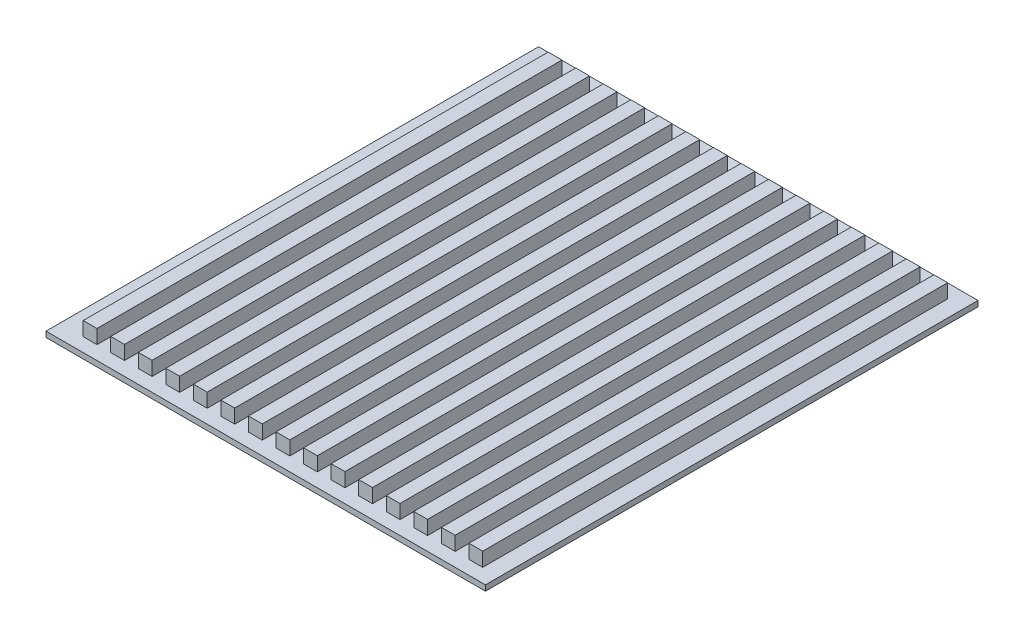
SolidWorks part; units mm, degrees
ref_plane "Front Plane" through (0, 0, 0) normal (0, 0, 1) x (1, 0, 0)
ref_plane "Top Plane" through (0, 0, 0) normal (0, 1, 0) x (1, 0, 0)
ref_plane "Right Plane" through (0, 0, 0) normal (1, 0, 0) x (0, 0, -1)
sketch "Sketch1" plane through (0, 0, 0) normal (0, 0, 1) x (1, 0, 0)
  line L0 (-297.4715, 336.2025) -> (7.3285, 336.2025) construction
  line L1 (-0.6715, 336.2025) -> (-10.6715, 336.2025)
  line L2 (-0.6715, 336.2025) -> (-0.6715, 322.0044)
  line L3 (-0.6715, 322.0044) -> (-10.6715, 322.0044)
  line L4 (-10.6715, 336.2025) -> (-10.6715, 322.0044)
  line L5 (7.3285, 326.0425) -> (7.3285, 336.2025) construction
  line L6 (-30.6715, 336.2025) -> (-30.6715, 322.0044)
  line L7 (-20.6715, 322.0044) -> (-30.6715, 322.0044)
  line L8 (-20.6715, 336.2025) -> (-20.6715, 322.0044)
  line L9 (-20.6715, 336.2025) -> (-30.6715, 336.2025)
  line L10 (-50.6715, 336.2025) -> (-50.6715, 322.0044)
  line L11 (-40.6715, 322.0044) -> (-50.6715, 322.0044)
  line L12 (-40.6715, 336.2025) -> (-40.6715, 322.0044)
  line L13 (-40.6715, 336.2025) -> (-50.6715, 336.2025)
  line L14 (-70.6715, 336.2025) -> (-70.6715, 322.0044)
  line L15 (-60.6715, 322.0044) -> (-70.6715, 322.0044)
  line L16 (-60.6715, 336.2025) -> (-60.6715, 322.0044)
  line L17 (-60.6715, 336.2025) -> (-70.6715, 336.2025)
  line L18 (-90.6715, 336.2025) -> (-90.6715, 322.0044)
  line L19 (-80.6715, 322.0044) -> (-90.6715, 322.0044)
  line L20 (-80.6715, 336.2025) -> (-80.6715, 322.0044)
  line L21 (-80.6715, 336.2025) -> (-90.6715, 336.2025)
  line L22 (-110.6715, 336.2025) -> (-110.6715, 322.0044)
  line L23 (-100.6715, 322.0044) -> (-110.6715, 322.0044)
  line L24 (-100.6715, 336.2025) -> (-100.6715, 322.0044)
  line L25 (-100.6715, 336.2025) -> (-110.6715, 336.2025)
  line L26 (-130.6715, 336.2025) -> (-130.6715, 322.0044)
  line L27 (-120.6715, 322.0044) -> (-130.6715, 322.0044)
  line L28 (-120.6715, 336.2025) -> (-120.6715, 322.0044)
  line L29 (-120.6715, 336.2025) -> (-130.6715, 336.2025)
  line L30 (-150.6715, 336.2025) -> (-150.6715, 322.0044)
  line L31 (-140.6715, 322.0044) -> (-150.6715, 322.0044)
  line L32 (-140.6715, 336.2025) -> (-140.6715, 322.0044)
  line L33 (-140.6715, 336.2025) -> (-150.6715, 336.2025)
  line L34 (-170.6715, 336.2025) -> (-170.6715, 322.0044)
  line L35 (-160.6715, 322.0044) -> (-170.6715, 322.0044)
  line L36 (-160.6715, 336.2025) -> (-160.6715, 322.0044)
  line L37 (-160.6715, 336.2025) -> (-170.6715, 336.2025)
  line L38 (-190.6715, 336.2025) -> (-190.6715, 322.0044)
  line L39 (-180.6715, 322.0044) -> (-190.6715, 322.0044)
  line L40 (-180.6715, 336.2025) -> (-180.6715, 322.0044)
  line L41 (-180.6715, 336.2025) -> (-190.6715, 336.2025)
  line L42 (-210.6715, 336.2025) -> (-210.6715, 322.0044)
  line L43 (-200.6715, 322.0044) -> (-210.6715, 322.0044)
  line L44 (-200.6715, 336.2025) -> (-200.6715, 322.0044)
  line L45 (-200.6715, 336.2025) -> (-210.6715, 336.2025)
  line L46 (-230.6715, 336.2025) -> (-230.6715, 322.0044)
  line L47 (-220.6715, 322.0044) -> (-230.6715, 322.0044)
  line L48 (-220.6715, 336.2025) -> (-220.6715, 322.0044)
  line L49 (-220.6715, 336.2025) -> (-230.6715, 336.2025)
  line L50 (-250.6715, 336.2025) -> (-250.6715, 322.0044)
  line L51 (-240.6715, 322.0044) -> (-250.6715, 322.0044)
  line L52 (-240.6715, 336.2025) -> (-240.6715, 322.0044)
  line L53 (-240.6715, 336.2025) -> (-250.6715, 336.2025)
  line L54 (-270.6715, 336.2025) -> (-270.6715, 322.0044)
  line L55 (-260.6715, 322.0044) -> (-270.6715, 322.0044)
  line L56 (-260.6715, 336.2025) -> (-260.6715, 322.0044)
  line L57 (-260.6715, 336.2025) -> (-270.6715, 336.2025)
  line L58 (-290.6715, 336.2025) -> (-290.6715, 322.0044)
  line L59 (-280.6715, 322.0044) -> (-290.6715, 322.0044)
  line L60 (-280.6715, 336.2025) -> (-280.6715, 322.0044)
  line L61 (-280.6715, 336.2025) -> (-290.6715, 336.2025)
  dimension "D1" = 10
  dimension "D2" = 8
  dimension "D3" = 15
extrude "Boss-Extrude1" add sketch "Sketch1" along normal up to surface (337.5607 mm away)
sketch "Sketch2" plane through (0, 0, 337.5607) normal (0, 0, 1) x (1, 0, 0)
  line L0 (-290.6715, 336.2025) -> (-290.6715, 322.0044) construction
  line L1 (-0.6715, 322.0044) -> (-290.6715, 322.0044)
  line L2 (-0.6715, 322.0044) -> (-0.6715, 326.0425)
  line L3 (-0.6715, 326.0425) -> (-290.6715, 326.0425)
  line L4 (-290.6715, 322.0044) -> (-290.6715, 326.0425)
  line L5 (-297.4715, 326.0425) -> (7.3285, 326.0425) construction
extrude "Boss-Extrude2" add sketch "Sketch2" against normal blind 10 and the other way blind 10
sketch "Sketch3" plane through (0, 0, 0) normal (0, 0, -1) x (-1, 0, 0)
  line L4 (0.6715, 322.0044) -> (290.6715, 322.0044)
  line L5 (290.6715, 322.0044) -> (290.6715, 326.0425)
  line L6 (290.6715, 326.0425) -> (0.6715, 326.0425)
  line L7 (0.6715, 326.0425) -> (0.6715, 322.0044)
  line L8 (0.6715, 322.0044) -> (290.6715, 322.0044)
  line L9 (290.6715, 322.0044) -> (290.6715, 326.0425)
  line L10 (290.6715, 326.0425) -> (0.6715, 326.0425)
  line L11 (0.6715, 326.0425) -> (0.6715, 322.0044)
  dimension "D1" = 0
extrude "Boss-Extrude3" add sketch "Sketch3" along normal blind 10 and the other way blind 10
sketch "Sketch4" plane through (-0.6715, 0, 0) normal (1, 0, 0) x (0, 0, -1)
  line L1 (10, 322.0044) -> (-347.5607, 322.0044)
  line L2 (10, 322.0044) -> (10, 326.0425)
  line L3 (10, 326.0425) -> (-347.5607, 326.0425)
  line L4 (-347.5607, 322.0044) -> (-347.5607, 326.0425)
extrude "Boss-Extrude4" add sketch "Sketch4" along normal blind 12
sketch "Sketch5" plane through (-290.6715, 0, 0) normal (-1, 0, 0) x (0, 0, 1)
  line L0 (337.5607, 326.0425) -> (0, 326.0425)
  line L8 (0, 336.2025) -> (0, 326.0425)
  line L9 (0, 326.0425) -> (-10, 326.0425)
  line L10 (-10, 326.0425) -> (-10, 322.0044)
  line L11 (-10, 322.0044) -> (347.5607, 322.0044)
  line L12 (347.5607, 322.0044) -> (347.5607, 326.0425)
  line L13 (347.5607, 326.0425) -> (337.5607, 326.0425)
  line L14 (337.5607, 326.0425) -> (337.5607, 336.2025)
  line L15 (337.5607, 336.2025) -> (0, 336.2025)
  line L16 (0, 336.2025) -> (0, 326.0425)
  line L17 (0, 326.0425) -> (-10, 326.0425)
  line L18 (-10, 326.0425) -> (-10, 322.0044)
  line L19 (-10, 322.0044) -> (347.5607, 322.0044)
  line L20 (347.5607, 322.0044) -> (347.5607, 326.0425)
  line L21 (347.5607, 326.0425) -> (337.5607, 326.0425)
  line L22 (337.5607, 326.0425) -> (337.5607, 336.2025)
  line L23 (337.5607, 336.2025) -> (0, 336.2025)
  line M10 (0, 326.0425) -> (-10, 326.0425)
  line M11 (-10, 326.0425) -> (-10, 322.0044)
  line M12 (-10, 322.0044) -> (347.5607, 322.0044)
  line M13 (347.5607, 322.0044) -> (347.5607, 326.0425)
  line M14 (347.5607, 326.0425) -> (337.5607, 326.0425)
  dimension "D1" = 0
extrude "Boss-Extrude6" add sketch "Sketch5" along normal blind 17 contours L0 M14 M10 M11 M12 M13 region at (-290.6715, 324.0234, 168.7803)
